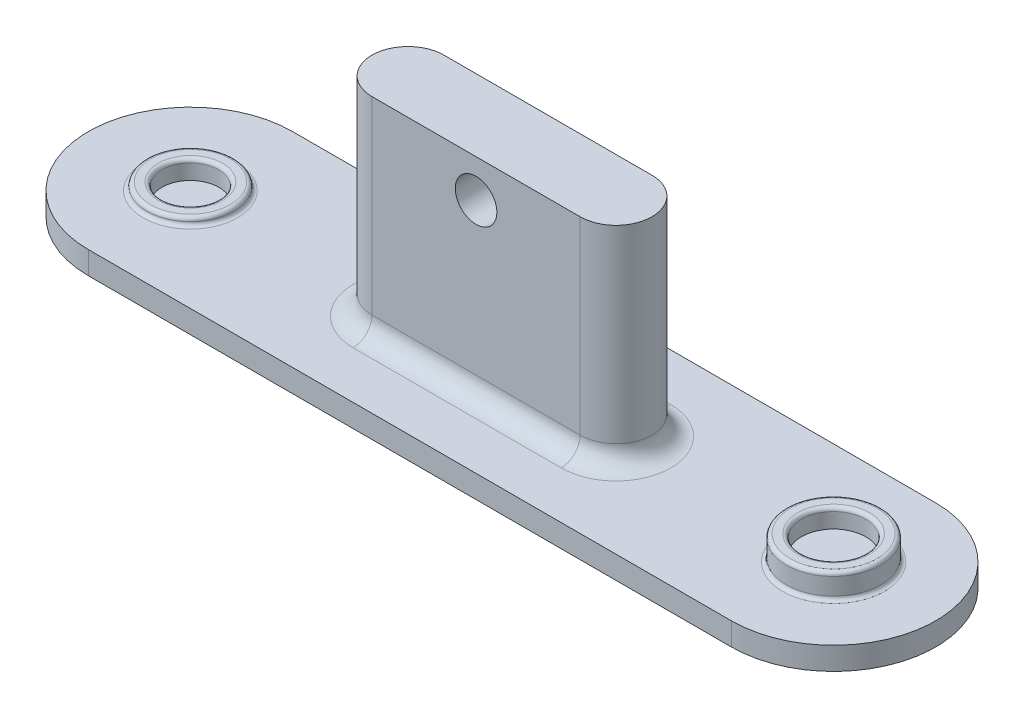
SolidWorks part; units mm, degrees
ref_plane "Front Plane" through (0, 0, 0) normal (0, 0, 1) x (1, 0, 0)
ref_plane "Top Plane" through (0, 0, 0) normal (0, 1, 0) x (1, 0, 0)
ref_plane "Right Plane" through (0, 0, 0) normal (1, 0, 0) x (0, 0, -1)
sketch "Sketch1" plane through (0, 0, 0) normal (0, 1, 0) x (1, 0, 0)
  line L0 (-142.4958, 0) -> (136.0591, 0) construction
  line L1 (0, 82.9006) -> (0, -67.1417) construction
  line L2 (-42.5, -13.5) -> (42.5, -13.5)
  line L3 (-42.5, 13.5) -> (42.5, 13.5)
  arc A0 (-42.5, 13.5) -> (-42.5, -13.5) centre (-42.5, 0) ccw
  arc A1 (42.5, 13.5) -> (42.5, -13.5) centre (42.5, 0) cw
  dimension "D1" = 85
  dimension "D2" = 27
extrude "Boss-Extrude1" add sketch "Sketch1" along normal blind 3
sketch "Sketch7" plane through (0, 3, 0) normal (0, 1, 0) x (1, 0, 0)
  circle A0 centre (-42.5, 0) radius 5.75
  arc A1 (-42.5, 13.5) -> (-42.5, -13.5) centre (-42.5, 0) ccw construction
  dimension "D1" = 11.5
extrude "Boss-Extrude5" add sketch "Sketch7" along normal blind 1
sketch "Sketch2" plane through (0, 4, 0) normal (0, 1, 0) x (1, 0, 0)
  circle A0 centre (-42.5, 0) radius 3.75
  arc A1 (-42.5, 13.5) -> (-42.5, -13.5) centre (-42.5, 0) ccw construction
  dimension "D1" = 7.5
extrude "Cut-Extrude1" cut sketch "Sketch2" against normal blind 2.5
sketch "Sketch3" plane through (0, 3, 0) normal (0, 1, 0) x (1, 0, 0)
  circle A0 centre (42.5, 0) radius 6.25
  arc A1 (42.5, -13.5) -> (42.5, 13.5) centre (42.5, 0) ccw construction
  dimension "D1" = 12.5
extrude "Boss-Extrude3" add sketch "Sketch3" along normal blind 3.25
sketch "Sketch4" plane through (0, 6.25, 0) normal (0, 1, 0) x (1, 0, 0)
  circle A0 centre (42.5, 0) radius 4.25
  circle A1 centre (42.5, 0) radius 6.25 construction
  dimension "D1" = 8.5
extrude "Cut-Extrude2" cut sketch "Sketch4" against normal blind 2.5
sketch "Sketch5" plane through (0, 3, 0) normal (0, 1, 0) x (1, 0, 0)
  line L0 (0, 28.1167) -> (0, -35.5844) construction
  line L1 (-13.75, 4.75) -> (13.75, 4.75)
  line L2 (-13.75, -4.75) -> (13.75, -4.75)
  arc A0 (-13.75, 4.75) -> (-13.75, -4.75) centre (-13.75, 0) ccw
  arc A1 (13.75, 4.75) -> (13.75, -4.75) centre (13.75, 0) cw
  dimension "D1" = 27.5
  dimension "D2" = 9.5
extrude "Boss-Extrude4" add sketch "Sketch5" along normal blind 27.5
sketch "Sketch6" plane through (0, 0, -4.75) normal (0, 0, -1) x (-1, 0, 0)
  line L2 (-13.75, 30.5) -> (13.75, 30.5) construction
  line L3 (0, -7.6238) -> (0, 35.8367) construction
  circle A0 centre (0, 25.5) radius 2.75
  dimension "D1" = 5
  dimension "D2" = 5.5
extrude "Cut-Extrude3" cut sketch "Sketch6" against normal through all
fillet "Fillet1" radius 0.5 6 edges at (-42.5, 4, 3.75) (-42.5, 4, 5.75) (-42.5, 3, 5.75) (42.5, 6.25, 4.25) (42.5, 6.25, 6.25) (42.5, 3, 6.25)
fillet "Fillet2" radius 2.5 4 edges at (18.5, 3, 0) (0, 3, 4.75) (-18.5, 3, 0) (0, 3, -4.75)
